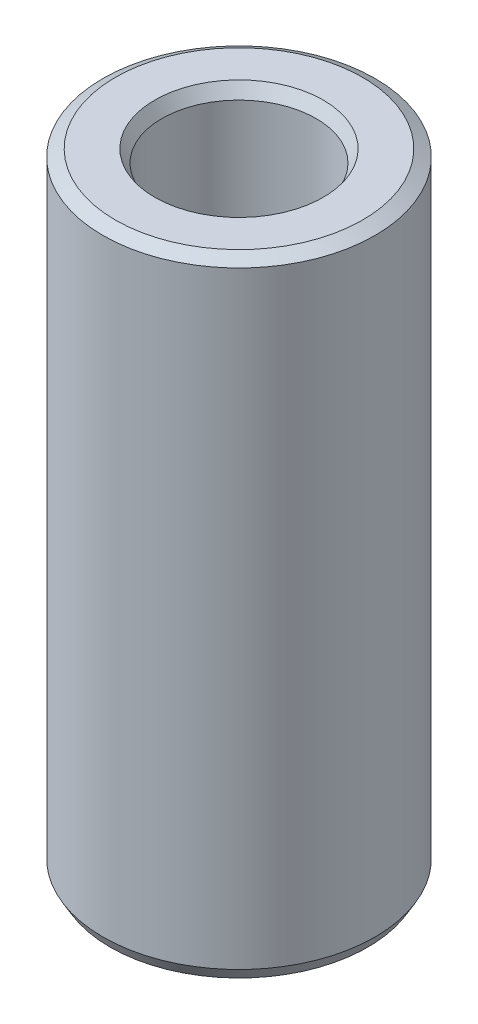
SolidWorks part; units mm, degrees
ref_plane "Front Plane" through (0, 0, 0) normal (0, 0, 1) x (1, 0, 0)
ref_plane "Top Plane" through (0, 0, 0) normal (0, 1, 0) x (1, 0, 0)
ref_plane "Right Plane" through (0, 0, 0) normal (1, 0, 0) x (0, 0, -1)
sketch "Sketch1" plane through (0, 0, 0) normal (0, 1, 0) x (1, 0, 0)
  circle A0 centre (0, 0) radius 15
  dimension "SLEEVE_OD" = 30
extrude "Boss-Extrude1" add sketch "Sketch1" along normal blind 69.1483
sketch "Sketch2" plane through (0, 0, 0) normal (0, 1, 0) x (1, 0, 0)
  circle A0 centre (0, 0) radius 8.5029
  dimension "BORE_D" = 17.0058
extrude "Cut-Extrude1" cut sketch "Sketch2" along normal through all
chamfer "Chamfer1" distance 0.7898 angle 60 4 edges at (0, 69.1483, 8.5029) (0, 0, 8.5029) (0, 0, 15) (0, 69.1483, 15) first distance on face at (0, 69.1483, 8.5029) first distance on face at (0, 0, 8.5029) first distance on face at (0, 69.1483, 15)
